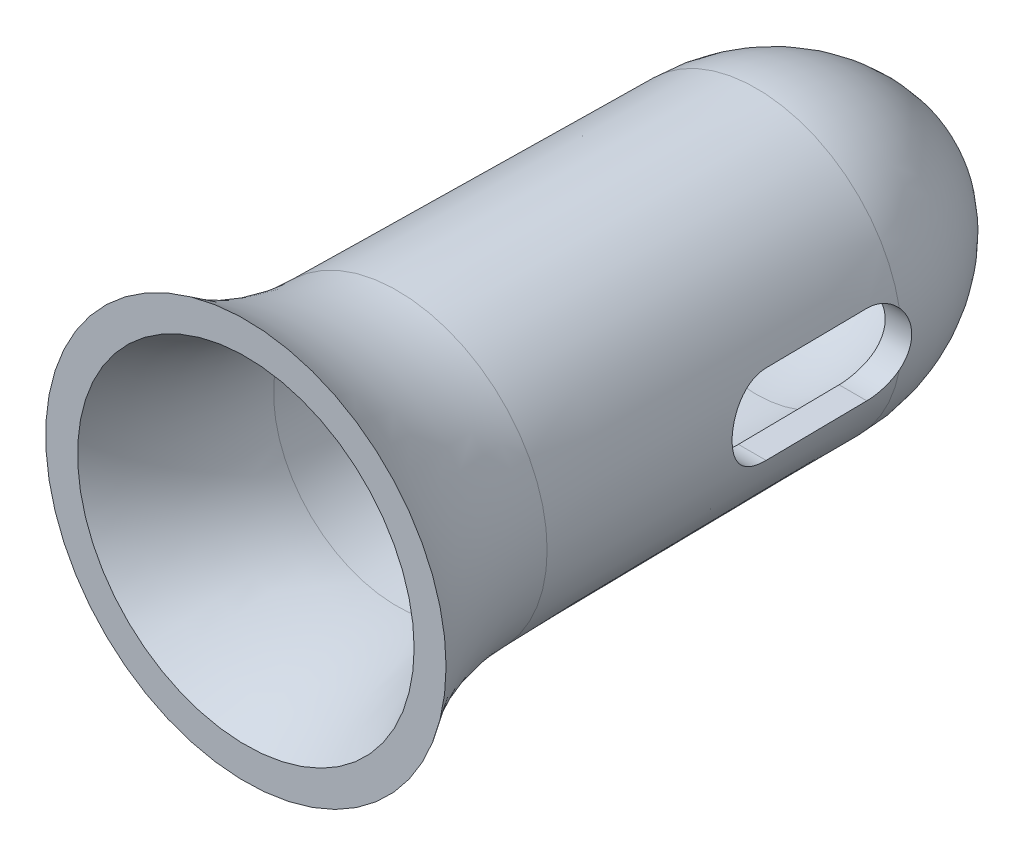
SolidWorks part; units mm, degrees
note: '?' marks a value the reader was unsure of.
material "ABS"
ref_plane "Front Plane" through (0, 0, 0) normal (0, 0, 1) x (1, 0, 0)
ref_plane "Top Plane" through (0, 0, 0) normal (0, 1, 0) x (1, 0, 0)
ref_plane "Right Plane" through (0, 0, 0) normal (1, 0, 0) x (0, 0, -1)
ref_axis "CentralAxis" through (0, 0, -72.8679) along (0, 0, 1)?
sketch "BottomRefProfileS" plane through (0, 0, 0) normal (0, 1, 0) x (1, 0, 0)
  line L0 (0, 0) -> (21.25, 0) construction
  line L1 (21.25, 0) -> (21.25, 23) construction
  line L2 (0, 0) -> (0, 23) construction
  line L3 (0, 23) -> (13.75, 23) construction
  line L4 (21.25, 0) -> (19.5, 0)
  line L5 (13.75, 23) -> (11.5558, 23)
  arc A1 (21.25, 0) -> (13.75, 23) centre (-17.7667, 0) ccw
  arc A2 (19.5, 0) -> (11.5558, 23) centre (-17.7667, 0) ccw
  dimension "D1" = 0
other "AlignGroup1" parameters "D4"=25.6215, "D2"=25.6215, "D1"=56.0592, "BottomDiameter"=42.5, "H1"=23, "TopDiameter"=27.5, "D3"=21.25, "WallThickness"=1.75
sketch "ProfileS" plane through (0, 0, 0) normal (0, 1, 0) x (1, 0, 0)
  line L0 (10, 58.0449) -> (10.2912, 33.3982)
  line L1 (13.75, 23) -> (11.5558, 23)
  line L2 (3.05, 69.3982) -> (3.05, 67.2998)
  line L4 (0, 23) -> (0, 69.3982) construction
  line L6 (8.1854, 58.0235) -> (8.4766, 33.3768)
  line L7 (0, 69.3982) -> (3.05, 69.3982) construction
  arc A0 (10.2912, 33.3982) -> (13.75, 23) centre (28.2899, 33.6109) ccw
  arc A1 (21.25, 0) -> (13.75, 23) centre (-17.7667, 0) ccw construction
  arc A2 (10, 58.0449) -> (3.05, 69.3982) centre (-2.9991, 57.8913) ccw
  arc A3 (8.4766, 33.3768) -> (11.5558, 23) centre (28.2899, 33.6109) ccw
  arc A4 (8.1854, 58.0235) -> (3.05, 67.2998) centre (-2.9991, 57.8913) ccw
  dimension "D1" = 13
  dimension "R1" = 18
  dimension "Height1" = 36
  dimension "Diameter1" = 20.5824
  dimension "Diameter3" = 6.1
  dimension "TopRadiusHeight" = 11.3533
  dimension "Diameter2" = 20
revolve "Profile" add sketch "ProfileS" angle 360 about L4
sketch "SideConnectionCutoutS" plane through (0, 0, 0) normal (1, 0, 0) x (0, 0, -1)
  line L0 (56, 0) -> (49, 0) construction
  line L1 (72.8679, 0) -> (-3.4699, 0) construction
  line L2 (56, -2.75) -> (49, -2.75)
  line L3 (56, 2.75) -> (49, 2.75)
  line L4 (58.75, 0) -> (69.3982, 0) construction
  line L5 (69.3982, 3.05) -> (69.3982, -3.05) construction
  line L6 (23, 13.75) -> (23, -13.75) construction
  arc A0 (56, -2.75) -> (56, 2.75) centre (56, 0) ccw
  arc A1 (49, 2.75) -> (49, -2.75) centre (49, 0) ccw
  point P5 (52.5, 0)
  point P10 (58.75, 0)
  point P11 (46.25, 0)
  dimension "D1" = 0
  dimension "X1" = 29.5
other "AlignGroup2" parameters "D1"=4.3016, "Width"=5.5, "Length"=12.5, "X1"=17, "D2"=10.898, "RefXDim"=10.6482
extrude "SideConnectionCutout" cut sketch "SideConnectionCutoutS" against normal through all both and the other way through all
